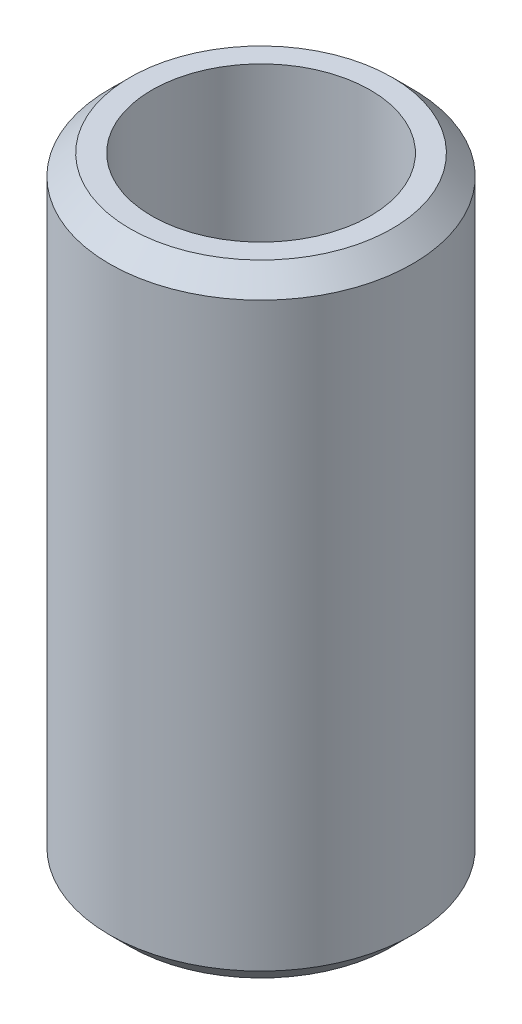
SolidWorks part; units mm, degrees
ref_plane "Front Plane" through (0, 0, 0) normal (0, 0, 1) x (1, 0, 0)
ref_plane "Top Plane" through (0, 0, 0) normal (0, 1, 0) x (1, 0, 0)
ref_plane "Right Plane" through (0, 0, 0) normal (1, 0, 0) x (0, 0, -1)
sketch "Sketch1" plane through (0, 0, 0) normal (0, 1, 0) x (1, 0, 0)
  circle A0 centre (0, 0) radius 37.5
  dimension "SHAFT_OD" = 75
extrude "Boss-Extrude1" add sketch "Sketch1" along normal blind 153.9525
sketch "Sketch2" plane through (0, 0, 0) normal (0, 1, 0) x (1, 0, 0)
  circle A0 centre (0, 0) radius 27.0344
  dimension "BORE_D" = 54.0687
extrude "Cut-Extrude1" cut sketch "Sketch2" along normal through all
chamfer "Chamfer1" distance 5.0419 angle 45 2 edges at (0, 153.9525, 37.5) (0, 0, 37.5)
